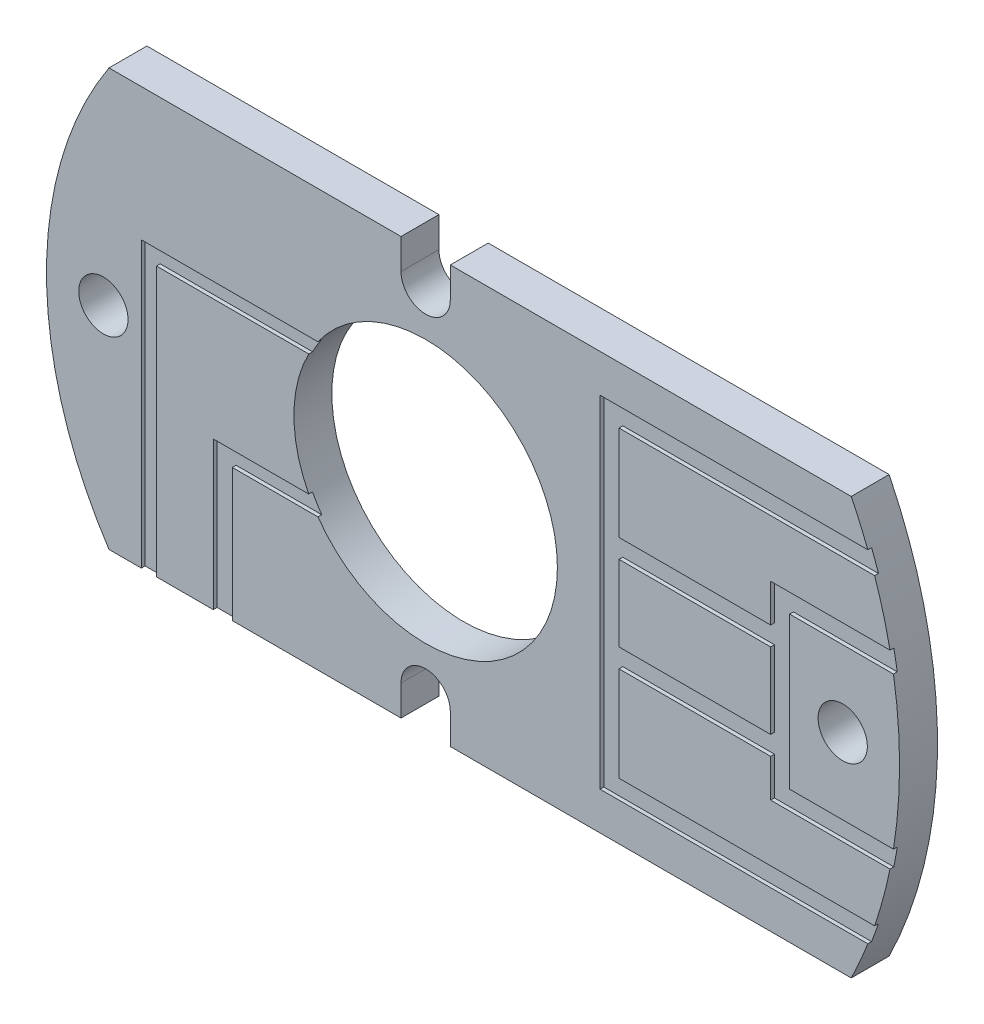
SolidWorks part; units mm, degrees
ref_plane "Спереди" through (0, 0, 0) normal (0, 0, 1) x (1, 0, 0)
ref_plane "Сверху" through (0, 0, 0) normal (0, 1, 0) x (1, 0, 0)
ref_plane "Справа" through (0, 0, 0) normal (1, 0, 0) x (0, 0, -1)
sketch "Model" plane through (0, 0, 0) normal (0, 0, 1) x (1, 0, 0)
  line L0 (0, 4.7) -> (0, -4.7) construction
  line L1 (0.65, -4.7) -> (0.65, -5.5)
  line L2 (0, 0) -> (11, 0) construction
  line L3 (-0.65, -4.7) -> (-0.65, -5.5)
  line L4 (0, 0) -> (-8.5, 0) construction
  line L5 (12.5, -5.5) -> (12.5, 5.5)
  line L6 (1.1, 0) -> (-6.8253, 0) construction
  line L7 (-10, -5.5) -> (-10, 5.5)
  line L8 (12.5, -5.5) -> (0.65, -5.5)
  line L9 (12.5, 5.5) -> (0.65, 5.5)
  line L12 (0.65, -4.7) -> (0.65, -5.5)
  line L13 (-0.65, -4.7) -> (-0.65, -5.5)
  line L14 (-0.65, 4.7) -> (-0.65, 5.5)
  line L15 (0.65, 4.7) -> (0.65, 5.5)
  line L16 (-0.65, 4.7) -> (-0.65, 5.5)
  line L17 (0.65, 4.7) -> (0.65, 5.5)
  line L19 (-0.65, 5.5) -> (-10, 5.5)
  line L20 (-0.65, -5.5) -> (-10, -5.5)
  arc A0 (0.65, -4.7) -> (-0.65, -4.7) centre (0, -4.7) ccw
  circle A1 centre (-8.5, 0) radius 0.65
  circle A25 centre (0, 0) radius 3.4746
  arc A28 (0.65, 4.7) -> (-0.65, 4.7) centre (0, 4.7) cw
  circle A33 centre (11, 0) radius 0.65
  point P27 (13, 0)
  point P45 (-11.5, 0)
  dimension "D1" = 9.4
  dimension "D6" = 11
  dimension "D2" = 12.5
  dimension "D8" = 10
  dimension "D9" = 8.5
extrude "Бобышка-Вытянуть1" add sketch "Model" along normal mid plane 1 contours A25 region at (0, -3.7996, 0)
sketch "Sketch1" plane through (0, 0, 0) normal (0, 0, 1) x (1, 0, 0)
  line L0 (0, 0) -> (5.152, 0) construction
  line L1 (17.9745, -9) -> (9.0799, -9)
  line L2 (17.9745, -9) -> (17.9745, 9)
  line L3 (17.9745, 9) -> (9.0799, 9)
  line L4 (9.0799, -9) -> (9.0799, 9)
  line L5 (-7.0718, -9) -> (-15.4961, -9)
  line L6 (-7.0718, -9) -> (-7.0718, 9)
  line L7 (-7.0718, 9) -> (-15.4961, 9)
  line L8 (-15.4961, -9) -> (-15.4961, 9)
  circle A0 centre (0, 0) radius 12.5
  circle A1 centre (0, 0) radius 10
  dimension "D1" = 9
  dimension "D2" = 9
  dimension "D3" = 9
  dimension "D4" = 9
extrude "Extrude1" cut sketch "Sketch1" against normal through all both and the other way through all contours A0 L0 A1 L6 L7 | L0 A0 L5 L6 A1 | A0 L0 L2 L3 L4 | L0 A0 L4 L1 L2 region at (14.5603, 0, 0) region at (-12.312, 0, 0)
sketch "Sketch2" plane through (0, 0, 0.5) normal (0, 0, 1) x (1, 0, 0)
  line L4 (0.65, -4.7) -> (0.65, -5.5)
  line L34 (-0.65, -4.7) -> (-0.65, -5.5)
  line L35 (-0.65, 4.7) -> (-0.65, 5.5)
  line L42 (0.65, 4.7) -> (0.65, 5.5)
  line L57 (11.225, 5.5) -> (0.65, 5.5)
  line L62 (6, -5.5) -> (0.65, -5.5)
  line L63 (-0.65, -5.5) -> (-8.3516, -5.5)
  line L64 (-0.65, 5.5) -> (-8.3516, 5.5)
  line L65 (6, -5.5) -> (11.225, -5.5)
  line L66 (-7.5, 2) -> (-7.5, -2)
  line L67 (-7.1, 1.6) -> (-7.1, -1.6)
  line L68 (-5.6, -1.6) -> (-4.1, -1.6)
  line L69 (-7.1, 1.6) -> (-4.1, 1.6)
  line L70 (-7.1, 1.6) -> (-7.1, -1.6)
  line L71 (-7.5, 2) -> (-3.7, 2)
  line L72 (-5.1, -2) -> (-3.7, -2)
  line L73 (9.1, -1) -> (9.1, 1)
  line L74 (6.1, 1.5) -> (9.1, 1.5)
  line L75 (9.1, -1) -> (6.1, -1)
  line L76 (6.1, 1) -> (9.1, 1)
  line L82 (9.1, 2.5) -> (9.1, 1.5)
  line L83 (9.1, 1.5) -> (6.1, 1.5)
  line L84 (9.1, -1) -> (5.1, -1)
  line L85 (6.1, 1) -> (5.1, 1)
  line L86 (5.1, 1) -> (5.1, -1)
  line L87 (6.1, 1.5) -> (5.1, 1.5)
  line L88 (5.1, 0.814) -> (5.1, 1)
  line L89 (5.1, 1.5) -> (5.1, 4)
  line L90 (6.1, -1.5) -> (9.1, -1.5)
  line L91 (9.1, -1.5) -> (6.1, -1.5)
  line L92 (6.1, -1.5) -> (5.1, -1.5)
  line L93 (-3.7, -2) -> (-2.8413, -2)
  line L94 (-4.1, -1.6) -> (-3.0843, -1.6)
  line L95 (-4.1, 1.6) -> (-3.0843, 1.6)
  line L96 (-3.7, 2) -> (-2.8413, 2)
  line L97 (-7.1, -1.6) -> (-7.1, -5.5)
  line L98 (-7.5, -2) -> (-7.5, -5.5)
  line L99 (-7.1, -5.5) -> (-5.6, -5.5)
  line L100 (-5.6, -5.5) -> (-5.6, -1.6)
  line L101 (-5.1, -2) -> (-5.1, -5.5)
  line L102 (9.6, -1.5) -> (9.6, 1.5)
  line L103 (4.6, -1.5) -> (4.6, 1.5)
  line L104 (4.6, 1.5) -> (4.6, 4)
  line L105 (5.1, 4) -> (9.1, 4)
  line L106 (9.6, 1.5) -> (9.6, 2)
  line L107 (9.6, 2) -> (12.339, 2)
  line L108 (9.1, 4) -> (11.8427, 4)
  line L109 (9.1, 2.5) -> (12.2474, 2.5)
  line L110 (4.6, 4) -> (4.6, 4.5)
  line L111 (4.6, 4.5) -> (11.6619, 4.5)
  line L112 (6.1, -1.5) -> (9.1, -1.5)
  line L113 (9.1, -2.5) -> (9.1, -1.5)
  line L114 (9.1, -1.5) -> (6.1, -1.5)
  line L115 (6.1, -1.5) -> (5.1, -1.5)
  line L116 (5.1, -1.5) -> (5.1, -4)
  line L117 (4.6, -1.5) -> (4.6, -4)
  line L118 (5.1, -4) -> (9.1, -4)
  line L119 (9.6, -1.5) -> (9.6, -2)
  line L120 (9.6, -2) -> (12.339, -2)
  line L121 (9.1, -4) -> (11.8427, -4)
  line L122 (9.1, -2.5) -> (12.2474, -2.5)
  line L123 (4.6, -4) -> (4.6, -4.5)
  line L124 (4.6, -4.5) -> (11.6619, -4.5)
  circle A0 centre (0, 0) radius 3.4746
  circle A1 centre (-8.5, 0) radius 0.65
  arc A2 (0.65, -4.7) -> (-0.65, -4.7) centre (0, -4.7) ccw
  arc A3 (-8.3516, 5.5) -> (-8.3516, -5.5) centre (0, 0) ccw
  arc A4 (-0.65, 4.7) -> (0.65, 4.7) centre (0, 4.7) ccw
  arc A5 (12.5, 0) -> (11.225, 5.5) centre (0, 0) ccw
  arc A6 (11.65, 0) -> (10.35, 0) centre (11, 0) ccw
  arc A7 (11.225, -5.5) -> (12.5, 0) centre (0, 0) ccw
  arc A8 (10.35, 0) -> (11.65, 0) centre (11, 0) ccw
  point P8 (6.1, 1.4)
  point P9 (6.1, -1.4)
  circle M98 centre (0, 0) radius 3.4746
  arc M100 (11.225, -5.5) -> (11.225, 5.5) centre (0, 0) ccw
  line M107 (-8.3516, -5.5) -> (-0.65, -5.5)
extrude "Extrude2" cut sketch "Sketch2" against normal blind 0.1 contours L101 L72 L93 L94 L68 L100 M98 M107 | L66 L98 L63 L97 L67 L69 L95 L96 L71 M98 | L123 L124 L121 L118 L116 L92 L90 L113 L122 L120 L119 L102 L106 L107 L109 L82 L74 L87 L89 L105 L108 L111 L110 L104 L103 L117 L86 L85 L76 L73 L75 L84 M100 region at (-5.35, -5.4522, 0.5) region at (8.131, -4.3813, 0.5) region at (-7.3, -5.4117, 0.5)
